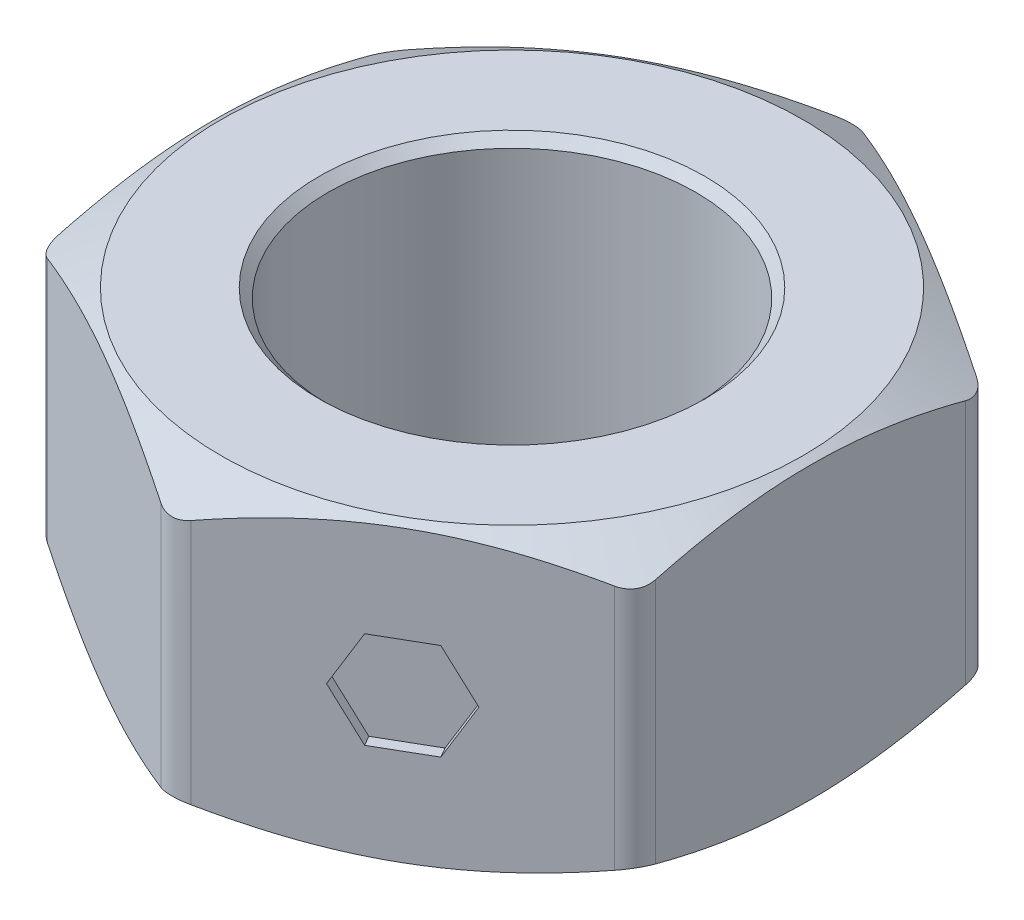
SolidWorks part; units mm, degrees
material "Alloy Steel"
ref_plane "Front Plane" through (0, 0, 0) normal (0, 0, 1) x (1, 0, 0)
ref_plane "Top Plane" through (0, 0, 0) normal (0, 1, 0) x (1, 0, 0)
ref_plane "Right Plane" through (0, 0, 0) normal (1, 0, 0) x (0, 0, -1)
sketch "Sketch1" plane through (0, 0, 0) normal (0, 0, 1) x (1, 0, 0)
  line L0 (0, -3.25) -> (0, 3.25) construction
  line L1 (6.5, 0) -> (-6.5, 0) construction
  line L2 (4, -3.25) -> (-4, -3.25) construction
  line L3 (4, -3.25) -> (4, -2) construction
  point P4 (0, 0)
  point P8 (0, 0)
  point P11 (0, -3.25)
  dimension "Height" = 6.5
  dimension "Width" = 13
  dimension "Thread Size" = 8
  dimension "Thread Pitch" = 1.25
sketch "Sketch2" plane through (0, 0, 0) normal (0, 1, 0) x (1, 0, 0)
  line L1 (0, 7.5056) -> (-6.5, 3.7528)
  line L2 (-6.5, 3.7528) -> (-6.5, -3.7528)
  line L3 (-6.5, -3.7528) -> (0, -7.5056)
  line L4 (0, -7.5056) -> (6.5, -3.7528)
  line L5 (6.5, -3.7528) -> (6.5, 3.7528)
  line L6 (6.5, 3.7528) -> (0, 7.5056)
  circle A0 centre (0, 0) radius 6.5 construction
  circle A1 centre (0, 0) radius 4
  point P19 (0, -4)
extrude "Boss-Extrude1" add sketch "Sketch2" along normal up to vertex (3.25 mm away) and the other way up to vertex (3.25 mm away) up to point (0, 3.25, 0) other way up to point (0, -3.25, 0)
fillet "Fillet1" radius 0.65 6 edges at (-6.5, 0, -3.7528) (0, 0, -7.5056) (-6.5, 0, 3.7528) (6.5, 0, -3.7528) (6.5, 0, 3.7528) (0, 0, 7.5056)
sketch "Sketch3" plane through (0, 0, 0) normal (1, 0, 0) x (0, 0, -1)
  line L2 (6.3375, -3.25) -> (7.5056, -2.5756)
  line L3 (3.9404, -3.25) -> (7.3179, -3.25) construction
  line L4 (7.5056, 3.25) -> (7.5056, -3.25) construction
  line L5 (7.5056, -2.5756) -> (7.5056, -3.25)
  line L6 (7.5056, -3.25) -> (6.3375, -3.25)
  line L12 (3.9404, 3.25) -> (7.3179, 3.25) construction
  line L16 (4, 3.25) -> (4, 3.05)
  line L17 (4, 3.25) -> (4.2, 3.25)
  line L21 (4, -3.25) -> (4, -3.05)
  line L22 (-3.3775, -3.25) -> (3.3775, -3.25) construction
  line L24 (4.2, -3.25) -> (4, -3.25)
  line L25 (4, -3.05) -> (4.2, -3.25)
  line L26 (4.2, 3.25) -> (4, 3.05)
  line L28 (0, -3.25) -> (0, 3.25) construction
  line L29 (0, -3.25) -> (0, 3.25) construction
  line L33 (6.3375, 3.25) -> (7.5056, 2.5756)
  line L34 (6.3375, 3.25) -> (6.5, 3.25) construction
  line L35 (4, 0) -> (6.5, 0) construction
  line L36 (4, -3.25) -> (4, 3.25) construction
  line L37 (3.9404, -3.25) -> (7.3179, -3.25) construction
  line L38 (6.5, 3.25) -> (6.5, 0) construction
  line L43 (7.5056, 2.5756) -> (7.5056, 3.25)
  line L47 (7.5056, 3.25) -> (6.3375, 3.25)
  point P1 (6.5, 0)
  point P14 (4, 0)
  dimension "D2" = 30
  dimension "D5" = 0.2
  dimension "D1" = 30
  dimension "D3" = 0.1625
revolve "Cut-Revolve2" cut sketch "Sketch3" angle 360 about L0
sketch "Sketch12" plane through (3.25, 0, 5.6292) normal (0.5, 0, 0.866) x (0.866, 0, -0.5)
  line L0 (0, 3.1562) -> (0, 1.0521) construction
  line L1 (0, 1.0521) -> (0, -1.0521) construction
  line L2 (0, -1.0521) -> (0, -3.1562) construction
  line L5 (-1.2148, 0) -> (-0.6074, -1.0521)
  line L6 (-0.6074, -1.0521) -> (0.6074, -1.0521)
  line L7 (0.6074, -1.0521) -> (1.2148, 0)
  line L8 (1.2148, 0) -> (0.6074, 1.0521)
  line L9 (0.6074, 1.0521) -> (-0.6074, 1.0521)
  line L10 (-0.6074, 1.0521) -> (-1.2148, 0)
  circle A0 centre (0, 0) radius 1.0521 construction
  spline S0 degree 3 poles (3.3775, 2.6798) (2.2712, 2.9743) (1.1516, 3.1551) (-0.2743, 3.1565) (-0.5618, 3.1457) (-1.1332, 3.1031) (-1.4172, 3.0713) (-2.2646, 2.9475) (-2.8233, 2.8273) (-3.3775, 2.6798) knots 0 0 0 0 0.5 0.5 0.625 0.625 0.75 0.75 1 1 1 1 construction
  spline S1 degree 3 poles (-3.3775, -2.6798) (-2.2712, -2.9743) (-1.1516, -3.1551) (0.2743, -3.1565) (0.5618, -3.1457) (1.1332, -3.1031) (1.4172, -3.0713) (2.2646, -2.9475) (2.8233, -2.8273) (3.3775, -2.6798) knots 0 0 0 0 0.5 0.5 0.625 0.625 0.75 0.75 1 1 1 1 construction
  point P9 (0, 0)
extrude "Cut-Extrude2" cut sketch "Sketch12" against normal blind 0.25
sketch "Sketch5" plane through (0, 0, 0) normal (0, 1, 0) x (1, 0, 0)
  circle A2 centre (0, 0) radius 4 construction
  point P0 (0, -4)
sketch "Sketch6" [suppressed] plane through (0, 0, 0) normal (0, 0, 1) x (1, 0, 0)
  line L0 (4, 3.25) -> (4, -3.25)
  line L2 (0, -3.25) -> (6.5, -3.25) construction
  line L3 (4, -3.25) -> (0, -3.25)
  line L4 (0, -3.25) -> (0, 3.25)
  line L5 (0, -3.25) -> (0, 3.25) construction
  line L6 (0, 3.25) -> (4, 3.25)
revolve "Revolve2" [suppressed] add sketch "Sketch6" angle 360 about L4
sketch "Sketch7" [suppressed] plane through (0, -3.25, 0) normal (0, -1, 0) x (1, 0, 0)
  circle A2 centre (0, 0) radius 4
  circle A3 centre (0, 0) radius 4
  dimension "D1" = 0
curve "Helix/Spiral1" [suppressed] pitch 1.25 height 7.75 turns 6.2
sketch "Sketch8" [suppressed] plane through (0, 0, 0) normal (0, 0, 1) x (1, 0, 0)
  line L0 (4.1353, -3.1719) -> (3.0528, -3.7969) construction
  line L1 (3.0528, -3.7969) -> (4.1353, -4.4219) construction
  line L2 (4.1353, -4.4219) -> (4.1353, -3.1719) construction
  line L3 (3.1881, -3.7187) -> (3.1881, -3.875)
  line L4 (4, -3.25) -> (4, -4.3437) construction
  line L5 (4, -3.7969) -> (4.1353, -3.7969) construction
  line L6 (3.0528, -3.7969) -> (3.1881, -3.7969) construction
  line L7 (4.0677, -3.7969) -> (4.0677, -4.3828) construction
  line L8 (3.1881, -3.7187) -> (4.1353, -3.1719)
  line L9 (4.1353, -3.1719) -> (4.0677, -4.3828)
  line L10 (3.1881, -3.875) -> (4.0677, -4.3828)
  dimension "D1" = 1.25
  dimension "D2" = 0.1562
sweep "Cut-Sweep1" [suppressed] cut profiles "Sketch8" path "Helix/Spiral1"
sketch "Sketch9" [suppressed] plane through (0, 0, 0) normal (0, 0, 1) x (1, 0, 0)
  line L0 (0, 0.75) -> (0, -3.25)
  line L1 (0, 0.75) -> (0, 0.95)
  line L2 (0, -3.25) -> (4, -3.25)
  line L3 (4, -3.25) -> (4.2, -3.25)
  line L4 (4.2, -3.25) -> (0, 0.95)
  dimension "D1" = 0.2
revolve "Revolve3" [suppressed] add sketch "Sketch9" angle 360 about L0
sketch "Sketch11" [suppressed] plane through (0, 0, 0) normal (0, 0, 1) x (1, 0, 0)
  line L0 (0, 3.25) -> (0, -0.4375)
  line L1 (0, -3.25) -> (0, 3.25) construction
  line L2 (0, -0.4375) -> (4.2, 3.25)
  line L3 (4.2, 3.25) -> (0, 3.25)
  spline S0 degree 2 poles (-1.1661, -2.2381) (-1.7845, -2.1956) (-2.2543, -2.1562) (-3.1881, -2.0781) (-3.1881, -2) (-3.1881, -1.9219) (-2.2543, -1.8437) (-1.3206, -1.7656) (0, -1.6875) (1.3206, -1.6094) (2.2543, -1.5312) (3.1881, -1.4531) (3.1881, -1.375) (3.1881, -1.2969) (2.2543, -1.2187) (1.3206, -1.1406) (0, -1.0625) (-1.3206, -0.9844) (-2.2543, -0.9062) (-3.1881, -0.8281) (-3.1881, -0.75) (-3.1881, -0.6719) (-2.2543, -0.5937) (-1.3206, -0.5156) (0, -0.4375) (1.3206, -0.3594) (2.2543, -0.2812) (3.1881, -0.2031) (3.1881, -0.125) (3.1881, -0.0469) (2.2543, 0.0313) (1.3206, 0.1094) (0, 0.1875) (-1.3206, 0.2656) (-2.2543, 0.3438) (-3.1881, 0.4219) (-3.1881, 0.5) (-3.1881, 0.5781) (-2.2543, 0.6563) (-1.3206, 0.7344) (0, 0.8125) (1.3206, 0.8906) (2.2543, 0.9688) (3.1881, 1.0469) (3.1881, 1.125) (3.1881, 1.2031) (2.2543, 1.2813) (1.3206, 1.3594) (0, 1.4375) (-1.3206, 1.5156) (-2.2543, 1.5938) (-3.1881, 1.6719) (-3.1881, 1.75) (-3.1881, 1.8281) (-2.2543, 1.9063) (-1.3206, 1.9844) (0, 2.0625) (1.3206, 2.1406) (2.2543, 2.2188) (3.1881, 2.2969) (3.1881, 2.375) (3.1881, 2.4531) (2.2543, 2.5313) (1.3206, 2.6094) (0, 2.6875) (-1.3206, 2.7656) (-2.2543, 2.8438) (-3.1881, 2.9219) (-3.1881, 3) (-3.1881, 3.0781) (-2.2543, 3.1563) (-1.7154, 3.2013) (-0.991, 3.25) knots 0.288704 0.288704 0.288704 0.296875 0.296875 0.3125 0.3125 0.328125 0.328125 0.34375 0.34375 0.359375 0.359375 0.375 0.375 0.390625 0.390625 0.40625 0.40625 0.421875 0.421875 0.4375 0.4375 0.453125 0.453125 0.46875 0.46875 0.484375 0.484375 0.5 0.5 0.515625 0.515625 0.53125 0.53125 0.546875 0.546875 0.5625 0.5625 0.578125 0.578125 0.59375 0.59375 0.609375 0.609375 0.625 0.625 0.640625 0.640625 0.65625 0.65625 0.671875 0.671875 0.6875 0.6875 0.703125 0.703125 0.71875 0.71875 0.734375 0.734375 0.75 0.75 0.765625 0.765625 0.78125 0.78125 0.796875 0.796875 0.8125 0.8125 0.828125 0.828125 0.837443 0.837443 0.837443 weights 0.96202 0.960193 1 0.92388 1 0.92388 1 0.92388 1 0.92388 1 0.92388 1 0.92388 1 0.92388 1 0.92388 1 0.92388 1 0.92388 1 0.92388 1 0.92388 1 0.92388 1 0.92388 1 0.92388 1 0.92388 1 0.92388 1 0.92388 1 0.92388 1 0.92388 1 0.92388 1 0.92388 1 0.92388 1 0.92388 1 0.92388 1 0.92388 1 0.92388 1 0.92388 1 0.92388 1 0.92388 1 0.92388 1 0.92388 1 0.92388 1 0.92388 1 0.954607 0.963353 construction
revolve "Revolve4" [suppressed] add sketch "Sketch11" angle 360 about L0
sketch "Sketch10" [suppressed] plane through (0, -3.25, 0) normal (0, -1, 0) x (1, 0, 0)
  circle A0 centre (0, 0) radius 4.2 construction
  circle A1 centre (0, 0) radius 4.2
extrude "Boss-Extrude2" [suppressed] add sketch "Sketch10" against normal up to surface (6.5 mm away)
combine bodies "Combine1" [suppressed] operation type subtract main body 110 bodies to subtract 112
equation "\"D5@Sketch3\"=\"Thread Size@Sketch1\"*.025"
equation "\"D4@Helix/Spiral1\" = \"Thread Pitch@Sketch1\""
equation "\"D3@Helix/Spiral1\"=\"Height@Sketch1\"+\"Thread Pitch@Sketch1\""
equation "\"D1@Sketch8\" = \"Thread Pitch@Sketch1\""
equation "\"D2@Sketch8\" = \"Thread Pitch@Sketch1\" / 8"
equation "\"D1@Sketch9\"=\"Thread Size@Sketch1\" * .025"
equation "\"D1@Fillet1\"=\"Width@Sketch1\" * .05"
equation "\"D3@Sketch3\"=\"Width@Sketch1\"*.0125"
equation "\"D1@Cut-Extrude2\"=((\"Width@Sketch1\"-\"Thread Size@Sketch1\")/2)*.1"
